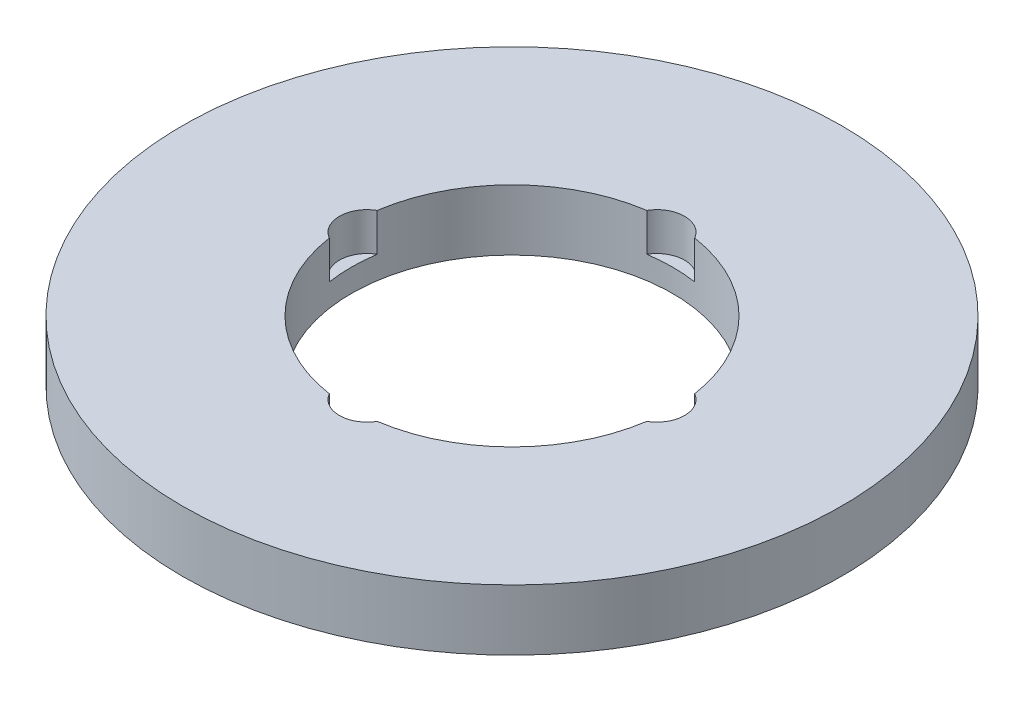
SolidWorks part; units mm, degrees
ref_plane "Front Plane" through (0, 0, 0) normal (0, 0, 1) x (1, 0, 0)
ref_plane "Top Plane" through (0, 0, 0) normal (0, 1, 0) x (1, 0, 0)
ref_plane "Right Plane" through (0, 0, 0) normal (1, 0, 0) x (0, 0, -1)
sketch "Sketch1" plane through (0, 0, 0) normal (0, 1, 0) x (1, 0, 0)
  circle A0 centre (0, 0) radius 97.5
  dimension "FLANGE_OD" = 195
extrude "Boss-Extrude1" add sketch "Sketch1" along normal blind 18
sketch "Sketch2" plane through (0, 0, 0) normal (0, 1, 0) x (1, 0, 0)
  circle A0 centre (0, 0) radius 47.5
  dimension "BORE_D" = 95
extrude "Cut-Extrude1" cut sketch "Sketch2" along normal through all
sketch "Sketch3" plane through (0, 18, 0) normal (0, 1, 0) x (1, 0, 0)
  circle A0 centre (0, 0) radius 42.8751 construction
  circle A1 centre (-42.8751, 0) radius 8.18
  dimension "BOLT_D" = 16.36
  dimension "BOLT_PCD" = 85.7502
extrude "Cut-Extrude2" cut sketch "Sketch3" against normal blind 11.2474
pattern_circular "CirPattern1" count 4 over 360 about axis through (0, 0, 0) along (0, 1, 0) of "Cut-Extrude2"
